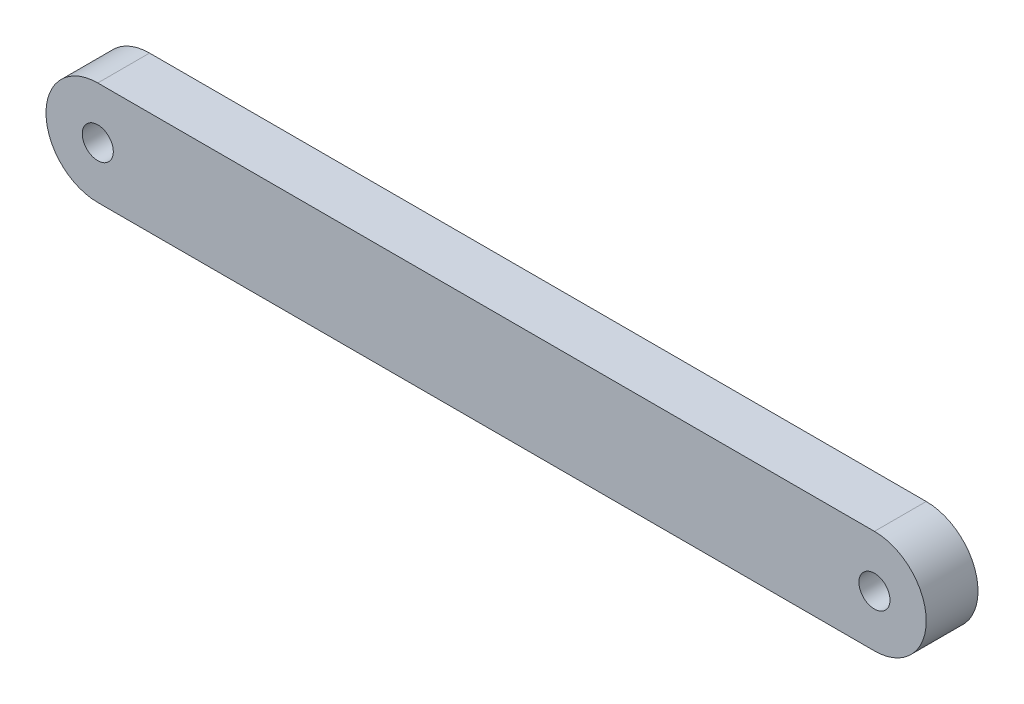
SolidWorks part; units mm, degrees
ref_plane "Piano frontale" through (0, 0, 0) normal (0, 0, 1) x (1, 0, 0)
ref_plane "Piano superiore" through (0, 0, 0) normal (0, 1, 0) x (1, 0, 0)
ref_plane "Piano destro" through (0, 0, 0) normal (1, 0, 0) x (0, 0, -1)
sketch "Sketch1" plane through (0, 0, 0) normal (0, 0, 1) x (1, 0, 0)
  line L0 (-375, 0) -> (375, 0) construction
  line L1 (-375, 50) -> (375, 50)
  line L2 (-375, -50) -> (375, -50)
  arc A0 (-375, 50) -> (-375, -50) centre (-375, 0) ccw
  arc A1 (375, -50) -> (375, 50) centre (375, 0) ccw
  point P3 (0, 0)
  dimension "D1" = 750
  dimension "D2" = 100
extrude "Boss-Extrude1" add sketch "Sketch1" along normal mid plane 50
sketch "Sketch2" plane through (0, 0, 25) normal (0, 0, 1) x (1, 0, 0)
  circle A0 centre (-375, 0) radius 15
  circle A1 centre (375, 0) radius 15
  dimension "D1" = 30
extrude "Cut-Extrude1" cut sketch "Sketch2" against normal through all
ref_axis "Axis1" through (-375, 0, -25) along (0, 0, 1)
ref_axis "Axis2" through (375, 0, -25) along (0, 0, 1)
ref_point "Point1"
ref_point "Point2"
